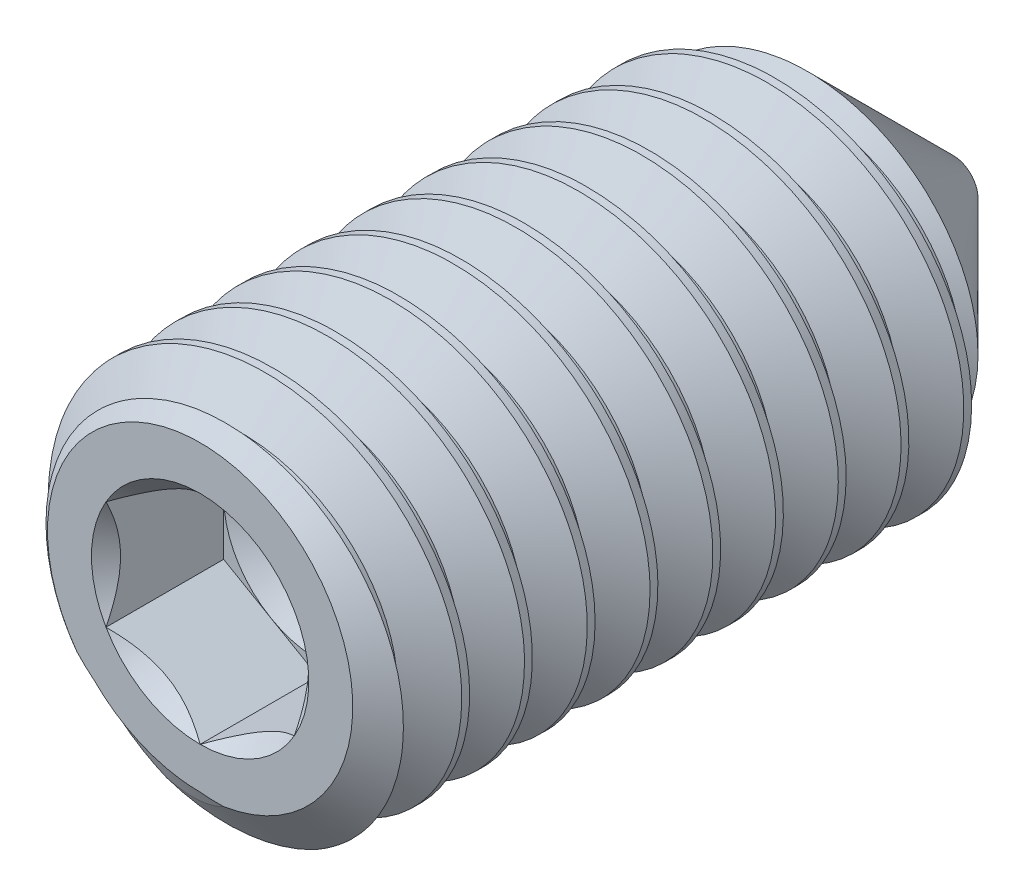
SolidWorks part; units mm, degrees
ref_plane "Front" through (0, 0, 0) normal (0, 0, 1) x (1, 0, 0)
ref_plane "Top" through (0, 0, 0) normal (0, 1, 0) x (1, 0, 0)
ref_plane "Right" through (0, 0, 0) normal (1, 0, 0) x (0, 0, -1)
sketch "Sketch22" plane through (0, 0, 0) normal (1, 0, 0) x (0, 0, -1)
  line L0 (-4.7625, 0) -> (-4.7625, 1.9304)
  line L1 (-4.7625, 1.9304) -> (-4.4246, 2.413)
  line L2 (-4.4246, 2.413) -> (2.6632, 2.413)
  line L3 (2.6632, 2.413) -> (4.7625, 0.3137)
  line L4 (-4.7625, 1.9304) -> (-4.7625, -1.9304) construction
  line L5 (4.7625, 0) -> (-4.7625, 0)
  line L6 (0, 2.413) -> (0, -2.413) construction
  line L8 (4.7625, 0.3137) -> (4.7625, 0)
  line L9 (-4.7625, -2.413) -> (4.7625, -2.413) construction
  line L10 (4.7625, 0.3137) -> (4.7625, -0.3137) construction
  line L11 (4.7625, -0.3137) -> (2.6632, -2.413) construction
  line L13 (4.7625, 0.3137) -> (4.4488, 0) construction
  line L15 (4.4488, 0) -> (4.7625, -0.3137) construction
  dimension "D3" = 35
  dimension "D7" = 3.8608
  dimension "Dia" = 4.826
  dimension "Length" = 9.525
  dimension "D2" = 0.6274
  dimension "D1" = 90
  dimension "D4" = 90
revolve "Revolve1" add sketch "Sketch22" angle 360 about L5
ref_plane "Plane1" through (0, 0, -4.7625) normal (0, 0, 1) x (1, 0, 0)
sketch "Sketch27" plane through (0, 0, -4.7625) normal (0, 0, 1) x (1, 0, 0)
  circle A0 centre (0, 0) radius 2.413 construction
  circle A1 centre (0, 0) radius 2.413
curve "Helix/Spiral1" pitch 0.7937 height 10.3188 radius 2.413 centre (0, 0, -4.7625) axis (0, 0, 1) start towards (0, 1, 0)
sketch "Sketch28" plane through (0, 0, 0) normal (1, 0, 0) x (0, 0, -1)
  line L0 (4.7625, 2.413) -> (5.457, 2.413)
  line L1 (5.457, 2.413) -> (5.1594, 1.8974)
  line L2 (5.1594, 1.8974) -> (5.0602, 1.8974)
  line L3 (5.0602, 1.8974) -> (4.7625, 2.413)
  line L4 (4.9113, 2.1552) -> (5.3082, 2.1552) construction
  line L6 (-4.4246, 2.413) -> (2.6632, 2.413) construction
  line L7 (4.7625, 2.6543) -> (4.7625, -2.6543) construction
  dimension "D1" = 0.0992
  dimension "D3" = 60
  dimension "D2" = 0.3969
sweep "Cut-Sweep2" cut profiles "Sketch28" path "Helix/Spiral1" align with end faces yes
sketch "Sketch23" plane through (0, 0, 4.7625) normal (0, 0, 1) x (1, 0, 0)
  line L1 (0, 1.3748) -> (-1.1906, 0.6874)
  line L2 (-1.1906, 0.6874) -> (-1.1906, -0.6874)
  line L3 (-1.1906, -0.6874) -> (0, -1.3748)
  line L4 (0, -1.3748) -> (1.1906, -0.6874)
  line L5 (1.1906, -0.6874) -> (1.1906, 0.6874)
  line L6 (1.1906, 0.6874) -> (0, 1.3748)
  circle A0 centre (0, 0) radius 1.1906 construction
  dimension "Hex" = 2.3813
extrude "Cut-Extrude10" cut sketch "Sketch23" against normal blind 1.4883
sketch "Sketch24" plane through (0, 0, 4.7625) normal (0, 0, 1) x (1, 0, 0)
  circle A0 centre (0, 0) radius 1.3748
extrude "Cut-Extrude11" cut sketch "Sketch24" against normal through all draft 45
sketch "Sketch26" plane through (0, 0, 3.2742) normal (0, 0, 1) x (1, 0, 0)
  circle A0 centre (0, 0) radius 1.1906 construction
  circle A1 centre (0, 0) radius 1.1906
extrude "Cut-Extrude12" cut sketch "Sketch26" against normal through all draft 60
sketch "Sketch30" plane through (0, 0, 0) normal (1, 0, 0) x (0, 0, -1)
  line L0 (-4.4246, 2.413) -> (2.6632, 2.413) construction
  line L1 (-4.7625, 0) -> (-4.7625, 1.9304) construction
  line L3 (-4.7625, -2.413) -> (4.7625, -2.413) construction
  point P0 (-4.7625, 2.413)
  point P1 (2.6632, 2.413)
  point P2 (2.6632, -2.413)
  point P11 (1.4726, -2.413)
  dimension "D1" = 1.1906
equation "\"D7@Sketch22\"=\"Dia@Sketch22\"*.8"
equation "\"D1@Sketch28\" = \"D4@Helix/Spiral1\" * .125"
equation "\"D3@Helix/Spiral1\" = \"Length@Sketch22\" + \"D4@Helix/Spiral1\""
equation "\"D1@Sketch30\" = \"D4@Helix/Spiral1\" * 1.5"
equation "\"hex Depth@Cut-Extrude10\" = \"Hex@Sketch23\" * .625"
equation "\"D2@Sketch28\" = \"D4@Helix/Spiral1\" * .5"
equation "\"D2@Sketch22\" = \"Dia@Sketch22\" * .13"
equation "\"D4@Sketch22\" = \"D1@Sketch22\""
